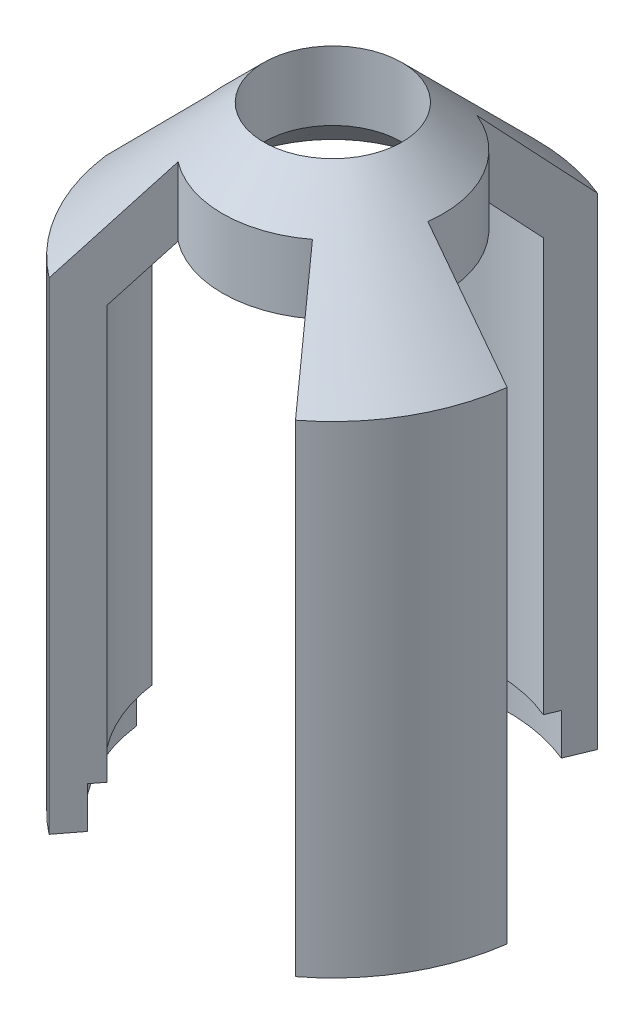
SolidWorks part; units mm, degrees
ref_plane "Front Plane" through (0, 0, 0) normal (0, 0, 1) x (1, 0, 0)
ref_plane "Top Plane" through (0, 0, 0) normal (0, 1, 0) x (1, 0, 0)
ref_plane "Right Plane" through (0, 0, 0) normal (1, 0, 0) x (0, 0, -1)
sketch "Sketch1" plane through (0, 0, 0) normal (0, 0, 1) x (1, 0, 0)
  line L0 (0, -8.9422) -> (0, 5.5778) construction
  line L1 (5.015, 41.685) -> (5.015, 36.685)
  line L2 (5.015, 36.685) -> (11.7, 30)
  line L3 (11.7, 30) -> (11.7, 0)
  line L4 (11.7, 0) -> (12.7, 0)
  line L5 (12.7, 0) -> (12.7, -3)
  line L6 (12.7, -3) -> (14.7, -3)
  line L7 (14.7, -3) -> (14.7, 32)
  line L10 (5.015, 41.685) -> (14.7, 32)
  point P1 (14.45, 11.4955)
  point P11 (6.4586, 21.9502)
  point P13 (0, 0)
  dimension "D1" = 10.03
  dimension "D2" = 25.4
  dimension "D3" = 1
  dimension "D4" = 2
  dimension "D5" = 3
  dimension "D6" = 30
  dimension "D7" = 45
  dimension "D8" = 5
revolve "Revolve1" add sketch "Sketch1" angle 360 about L0
sketch "Sketch2" plane through (0, -3, 0) normal (0, -1, 0) x (1, 0, 0)
  line L0 (-8.9488, 11.6623) -> (-4.8792, 6.3587)
  line L1 (8.9488, 11.6623) -> (4.8792, 6.3587)
  circle A0 centre (0, 0) radius 14.7 construction
  arc A1 (-8.9488, 11.6623) -> (8.9488, 11.6623) centre (0, 0) cw
  arc A2 (-4.8792, 6.3587) -> (4.8792, 6.3587) centre (0, 0) cw
  circle A3 centre (0, 0) radius 5.015 construction
  point P4 (0, 8.015)
  point P11 (5.9635, 4.9731)
  dimension "D2" = 3
  dimension "D1" = 75
extrude "Cut-Extrude1" cut sketch "Sketch2" against normal through all
pattern_circular "CirPattern1" count 3 over 360 about axis through (0, -8.9422, 0) along (0, -1, 0) of "Cut-Extrude1" reverse direction yes
